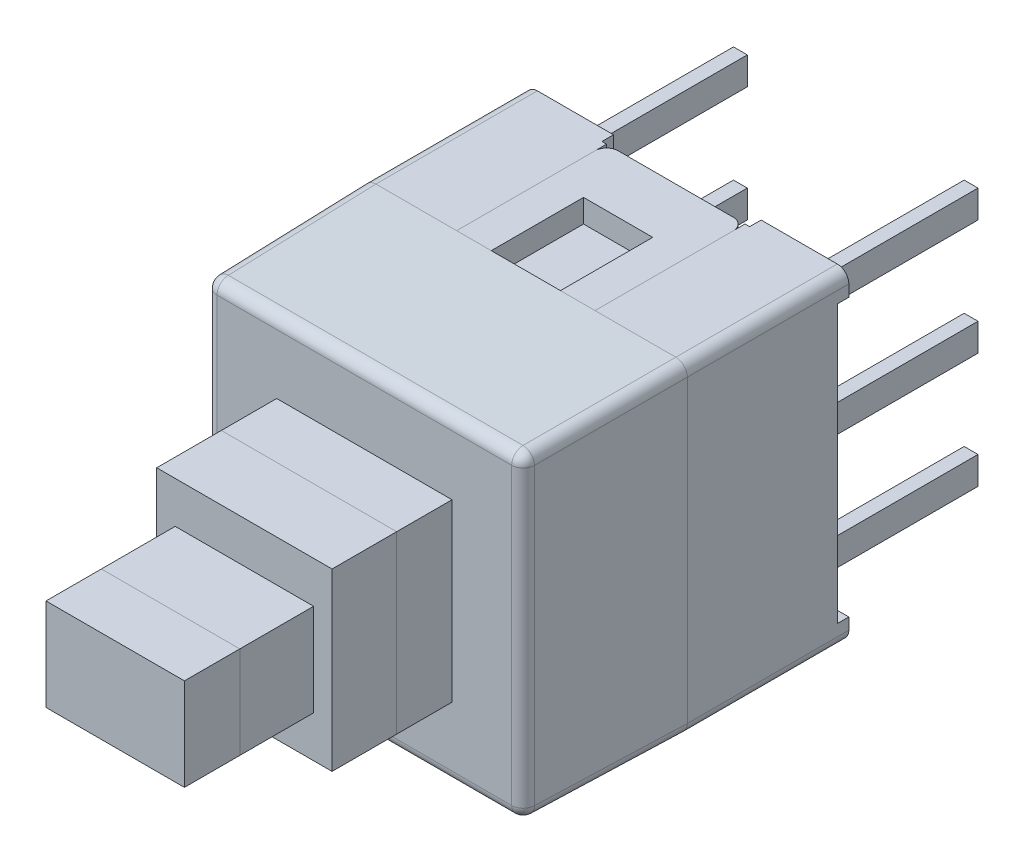
SolidWorks part; units mm, degrees
ref_plane "Plan de face" through (0, 0, 0) normal (0, 0, 1) x (1, 0, 0)
ref_plane "Plan de dessus" through (0, 0, 0) normal (0, 1, 0) x (1, 0, 0)
ref_plane "Plan de droite" through (0, 0, 0) normal (1, 0, 0) x (0, 0, -1)
sketch "Esquisse1" plane through (0, 0, 0) normal (0, 0, 1) x (1, 0, 0)
  line L1 (-3.5, -3.5) -> (3.5, -3.5)
  line L2 (-3.5, -3.5) -> (-3.5, 3.5)
  line L3 (-3.5, 3.5) -> (3.5, 3.5)
  line L4 (3.5, -3.5) -> (3.5, 3.5)
  line L5 (-3.5, -3.5) -> (3.5, 3.5) construction
  line L6 (-3.5, 3.5) -> (3.5, -3.5) construction
  point P0 (0, 0)
  dimension "D1" = 7
extrude "Boss.-Extru.1" add sketch "Esquisse1" along normal blind 3.5
sketch "Esquisse2" plane through (0, 0, 0) normal (0, 0, -1) x (-1, 0, 0)
  line L1 (-3.5, 3.5) -> (-1.6, 3.5)
  line L2 (-3.5, 3.5) -> (-3.5, 3)
  line L3 (-3.5, 3) -> (-1.6, 3)
  line L4 (-1.6, 3.5) -> (-1.6, 3)
  line L5 (3.5, 3.5) -> (1.6, 3.5)
  line L6 (3.5, 3.5) -> (3.5, 3)
  line L7 (3.5, 3) -> (1.6, 3)
  line L8 (1.6, 3.5) -> (1.6, 3)
  line L9 (3.5, -3.5) -> (1.6, -3.5)
  line L10 (3.5, -3.5) -> (3.5, -3)
  line L11 (3.5, -3) -> (1.6, -3)
  line L12 (1.6, -3.5) -> (1.6, -3)
  line L13 (-3.5, -3.5) -> (-1.6, -3.5)
  line L14 (-3.5, -3.5) -> (-3.5, -3)
  line L15 (-3.5, -3) -> (-1.6, -3)
  line L16 (-1.6, -3.5) -> (-1.6, -3)
  line L20 (-3.5, 3.5) -> (-3.5, -3.5)
  line L21 (-3.5, -3.5) -> (3.5, -3.5)
  line L22 (3.5, -3.5) -> (3.5, 3.5)
  line L23 (3.5, 3.5) -> (-3.5, 3.5)
  line L24 (-3.5, 3.5) -> (-3.5, -3.5)
  line L25 (-3.5, -3.5) -> (3.5, -3.5)
  line L26 (3.5, -3.5) -> (3.5, 3.5)
  line L27 (3.5, 3.5) -> (-3.5, 3.5)
  line M17 (-3.5, 3.5) -> (-3.5, -3.5)
  line M18 (-3.5, -3.5) -> (3.5, -3.5)
  line M19 (3.5, -3.5) -> (3.5, 3.5)
  line M20 (3.5, 3.5) -> (-3.5, 3.5)
  dimension "D1" = 0.5
  dimension "D2" = 1.9
  dimension "D3" = 0
extrude "Enlèv. mat.-Extru.1" cut sketch "Esquisse2" against normal blind 0.25 contours L16 L12 L11 L7 L8 L4 L3 L15 M18 M19 M20 M17 region at (0, 0, 0)
sketch "Esquisse3" plane through (0, 3.5, 0) normal (0, 1, 0) x (1, 0, 0)
  line L0 (-1.5, -0.25) -> (-1.5, -3.5)
  line L1 (-1.5, -0.25) -> (1.5, -0.25)
  line L2 (-1.5, -3.5) -> (1.5, -3.5)
  line L3 (1.5, -0.25) -> (1.5, -3.5)
  line L4 (-1.5, -0.25) -> (1.5, -3.5) construction
  line L5 (-1.5, -3.5) -> (1.5, -0.25) construction
  line L6 (-1.6, -0.25) -> (1.6, -0.25) construction
  line L7 (3.5, -3.5) -> (-3.5, -3.5) construction
  point P1 (0, -1.875)
  point P5 (0, 0)
  dimension "D1" = 3
extrude "Enlèv. mat.-Extru.2" cut sketch "Esquisse3" against normal blind 0.5
extrude "Enlèv. mat.-Extru.3" cut sketch "Esquisse3<2>" along normal blind 0.5 from surface starting at face at (0, -3.5, 0.9375)
sketch "Esquisse3<2>" plane through (0, 3.5, 0) normal (0, 1, 0) x (1, 0, 0) same geometry as "Esquisse3"
sketch "Esquisse4" plane through (0, 0, 3.5) normal (0, 0, 1) x (1, 0, 0)
  line L1 (-3.5, 3.5) -> (3.5, 3.5)
  line L2 (-3.5, 3.5) -> (-3.5, -3.5)
  line L3 (-3.5, -3.5) -> (3.5, -3.5)
  line L4 (3.5, 3.5) -> (3.5, -3.5)
extrude "Boss.-Extru.2" add sketch "Esquisse4" along normal blind 3.5 draft 1 separate body
sketch "Esquisse5" plane through (0, 0, 3.5) normal (0, 0, -1) x (-1, 0, 0)
  line L0 (-1.5, 3) -> (1.5, 3) construction
  line L1 (-1.5, 3.5) -> (1.5, 3.5)
  line L2 (-1.5, 3.5) -> (-1.5, 3)
  line L3 (-1.5, 3) -> (1.5, 3)
  line L4 (1.5, 3.5) -> (1.5, 3)
  line L5 (1.5, -3) -> (1.5, -3.5) construction
  line L6 (-1.5, -3.5) -> (1.5, -3.5)
  line L7 (-1.5, -3.5) -> (-1.5, -3)
  line L8 (-1.5, -3) -> (1.5, -3)
  line L9 (1.5, -3.5) -> (1.5, -3)
extrude "Boss.-Extru.3" add sketch "Esquisse5" along normal blind 3.25
sketch "Esquisse8" plane through (0, 0, 0) normal (0, 1, 0) x (1, 0, 0)
  line L1 (-0.75, -1.5) -> (0.75, -1.5)
  line L2 (-0.75, -1.5) -> (-0.75, -3.5)
  line L3 (-0.75, -3.5) -> (0.75, -3.5)
  line L4 (0.75, -1.5) -> (0.75, -3.5)
  line L5 (-1.5, -3.5) -> (1.5, -3.5) construction
  line L7 (-0.15, -1.5) -> (0.15, -1.5)
  line L8 (-0.15, -1.5) -> (-0.15, -3.5)
  line L9 (-0.15, -3.5) -> (0.15, -3.5)
  line L10 (0.15, -1.5) -> (0.15, -3.5)
  point P4 (0, -3.5)
  point P5 (0, -3.5)
  point P6 (0, 0)
  point P13 (0, 0)
  point P14 (0, 0)
  dimension "D1" = 1.5
  dimension "D2" = 2
  dimension "D3" = 0.3
extrude "Enlèv. mat.-Extru.4" cut sketch "Esquisse8" along normal through all contours L3 L4 L1 L2
extrude "Enlèv. mat.-Extru.5" cut sketch "Esquisse8<3>" against normal through all contours L1 L10 L3 L4 | L8 L1 L2 L3 region at (-0.45, 0, 2.5) region at (0.45, 0, 2.5)
sketch "Esquisse8<3>" plane through (0, 0, 0) normal (0, 1, 0) x (1, 0, 0) same geometry as "Esquisse8"
fillet "Congé1" radius 0.25 4 edges at (-3.5, -3.5, 1.75) (-3.5, 3.5, 1.75) (3.5, -3.5, 1.75) (3.5, 3.5, 1.75)
fillet "Congé2" radius 0.25 4 edges at (3.4695, 3.4695, 5.25) (3.4695, -3.4695, 5.25) (-3.4695, -3.4695, 5.25) (-3.4695, 3.4695, 5.25)
fillet "Congé3" radius 0.25 8 edges at (3.3657, -3.3657, 7) (0, -3.4389, 7) (-3.3657, -3.3657, 7) (-3.4389, 0, 7) (-3.3657, 3.3657, 7) (0, 3.4389, 7) (3.3657, 3.3657, 7) (3.4389, 0, 7)
fillet "Congé4" radius 0.25 4 edges at (-1.5, -3.25, 0.25) (-1.5, 3.25, 0.25) (1.5, 3.25, 0.25) (1.5, -3.25, 0.25)
sketch "Esquisse6" plane through (0, 0, 7) normal (0, 0, 1) x (1, 0, 0)
  line L2 (-1.9, -1.9) -> (1.9, -1.9)
  line L3 (-1.9, -1.9) -> (-1.9, 1.9)
  line L4 (-1.9, 1.9) -> (1.9, 1.9)
  line L5 (1.9, -1.9) -> (1.9, 1.9)
  line L6 (-1.9, -1.9) -> (1.9, 1.9) construction
  line L7 (-1.9, 1.9) -> (1.9, -1.9) construction
  point P0 (0, 0)
  point P2 (0, 0)
  dimension "D1" = 3.8
extrude "Boss.-Extru.4" add sketch "Esquisse6" along normal blind 1.2 separate body
extrude "Boss.-Extru.5" add sketch "Esquisse6<3>" along normal blind 1.4 from surface separate body starting at face at (0, 0, 8.2)
sketch "Esquisse6<3>" plane through (0, 0, 7) normal (0, 0, 1) x (1, 0, 0) same geometry as "Esquisse6"
sketch "Esquisse7" plane through (0, 0, 9.6) normal (0, 0, 1) x (1, 0, 0)
  line L1 (-1.5, -1) -> (1.5, -1)
  line L2 (-1.5, -1) -> (-1.5, 1)
  line L3 (-1.5, 1) -> (1.5, 1)
  line L4 (1.5, -1) -> (1.5, 1)
  line L5 (-1.5, -1) -> (1.5, 1) construction
  line L6 (-1.5, 1) -> (1.5, -1) construction
  point P0 (0, 0)
  dimension "D1" = 3
  dimension "D2" = 2
extrude "Boss.-Extru.6" add sketch "Esquisse7" along normal blind 1.6 and the other way up to surface (2.6 mm away) separate body other way up to face at (0, 0, 7)
extrude "Boss.-Extru.7" add sketch "Esquisse7<2>" along normal blind 1.2 from surface separate body starting at face at (0, 0, 11.2)
sketch "Esquisse7<2>" plane through (0, 0, 9.6) normal (0, 0, 1) x (1, 0, 0) same geometry as "Esquisse7"
sketch "Esquisse9" plane through (0, 0, 0.25) normal (0, 0, -1) x (-1, 0, 0)
  line L0 (0, 0) -> (2.5, 0) construction
  line L1 (0, 0) -> (0, 0.8912) construction
  line L2 (2.35, -2.2) -> (2.35, -2.8)
  line L3 (2.35, -0.3) -> (2.65, -0.3)
  line L4 (2.35, -0.3) -> (2.35, 0.3)
  line L5 (2.35, 0.3) -> (2.65, 0.3)
  line L6 (2.65, -0.3) -> (2.65, 0.3)
  line L7 (2.35, -0.3) -> (2.65, 0.3) construction
  line L8 (2.35, 0.3) -> (2.65, -0.3) construction
  line L9 (2.35, 2.2) -> (2.65, 2.2)
  line L10 (2.35, 2.2) -> (2.35, 2.8)
  line L11 (2.35, 2.8) -> (2.65, 2.8)
  line L12 (2.65, 2.2) -> (2.65, 2.8)
  line L13 (2.35, 2.2) -> (2.65, 2.8) construction
  line L14 (2.35, 2.8) -> (2.65, 2.2) construction
  line L15 (2.35, -2.8) -> (2.65, -2.8)
  line L16 (2.65, -2.2) -> (2.65, -2.8)
  line L17 (2.35, -2.2) -> (2.65, -2.2)
  line L18 (-2.35, 2.8) -> (-2.65, 2.8)
  line L19 (-2.65, 2.2) -> (-2.65, 2.8)
  line L20 (-2.35, 2.2) -> (-2.65, 2.2)
  line L21 (-2.35, 2.2) -> (-2.35, 2.8)
  line L22 (-2.35, 0.3) -> (-2.65, 0.3)
  line L23 (-2.65, -0.3) -> (-2.65, 0.3)
  line L24 (-2.35, -0.3) -> (-2.65, -0.3)
  line L25 (-2.35, -0.3) -> (-2.35, 0.3)
  line L26 (-2.35, -2.2) -> (-2.65, -2.2)
  line L27 (-2.65, -2.2) -> (-2.65, -2.8)
  line L28 (-2.35, -2.8) -> (-2.65, -2.8)
  line L29 (-2.35, -2.2) -> (-2.35, -2.8)
  point P8 (2.5, 2.5)
  point P13 (0, 0)
  point P14 (0, 0)
  point P15 (0, 0)
  dimension "D1" = 0.3
  dimension "D2" = 0.6
  dimension "D3" = 2.5
  dimension "D4" = 2.5
extrude "Boss.-Extru.8" add sketch "Esquisse9" along normal blind 3.9 separate body
